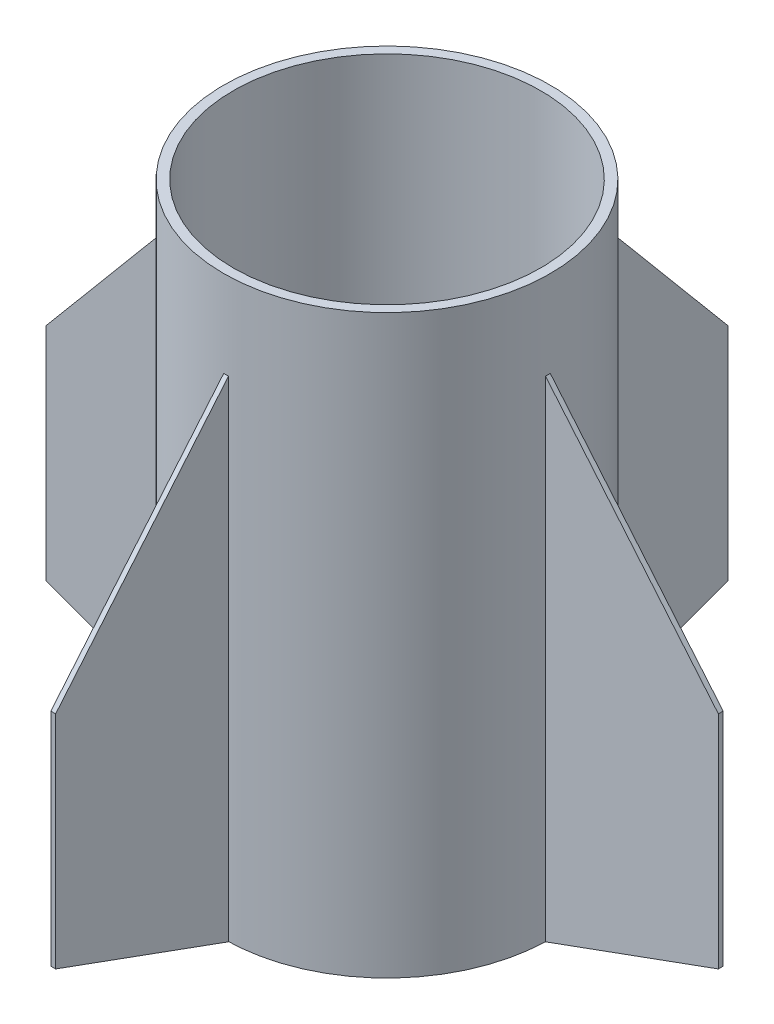
SolidWorks part; units mm, degrees
ref_plane "Front Plane" through (0, 0, 0) normal (0, 0, 1) x (1, 0, 0)
ref_plane "Top Plane" through (0, 0, 0) normal (0, 1, 0) x (1, 0, 0)
ref_plane "Right Plane" through (0, 0, 0) normal (1, 0, 0) x (0, 0, -1)
sketch "Sketch1" plane through (0, 0, 0) normal (0, 1, 0) x (1, 0, 0)
  circle A0 centre (0, 0) radius 101.6
  circle A1 centre (0, 0) radius 107.95
  dimension "D1" = 203.2
extrude "Boss-Extrude1" add sketch "Sketch1" along normal blind 381
sketch "Sketch2" plane through (0, 0, 0) normal (1, 0, 0) x (0, 0, -1)
  line L0 (-107.95, 323.85) -> (-222.25, 187.6577)
  line L1 (-107.95, 381) -> (-107.95, 0) construction
  line L2 (-222.25, 187.6577) -> (-222.25, 41.6077)
  line L3 (-222.25, 41.6077) -> (-107.95, 0)
  line L4 (-107.95, 0) -> (-107.95, 323.85)
  line L5 (0, 0) -> (0, 544.109) construction
  dimension "D1" = 114.3
  dimension "D2" = 177.8
  dimension "D3" = 323.85
  dimension "D4" = 146.05
extrude "Boss-Extrude2" add sketch "Sketch2" along normal blind 3.175 separate body
sketch "Sketch5" plane through (0, 0, 0) normal (1, 0, 0) x (0, 0, -1)
  line L0 (107.95, 323.85) -> (222.25, 187.6577)
  line L1 (107.95, 0) -> (107.95, 381) construction
  line L2 (222.25, 187.6577) -> (222.25, 41.6077)
  line L3 (222.25, 41.6077) -> (107.95, 0)
  line L4 (107.95, 0) -> (107.95, 381) construction
  line L5 (107.95, 323.85) -> (107.95, 0)
  dimension "D1" = 323.85
  dimension "D2" = 177.8
  dimension "D3" = 114.3
  dimension "D4" = 146.05
extrude "Boss-Extrude3" add sketch "Sketch5" along normal blind 3.175 separate body
sketch "Sketch6" plane through (0, 0, 0) normal (0, 0, 1) x (1, 0, 0)
  line L0 (-107.95, 323.85) -> (-222.25, 187.6577)
  line L1 (-107.95, 381) -> (-107.95, 0) construction
  line L2 (-222.25, 187.6577) -> (-222.25, 41.6077)
  line L3 (-222.25, 41.6077) -> (-107.95, 0)
  line L4 (-107.95, 323.85) -> (-107.95, 0)
  dimension "D1" = 146.05
  dimension "D2" = 177.8
  dimension "D3" = 323.85
  dimension "D4" = 114.3
extrude "Boss-Extrude4" add sketch "Sketch6" along normal blind 3.175 separate body
sketch "Sketch7" plane through (0, 0, 0) normal (0, 0, 1) x (1, 0, 0)
  line L0 (107.95, 323.85) -> (222.25, 187.6577)
  line L1 (107.95, 0) -> (107.95, 381) construction
  line L2 (222.25, 187.6577) -> (222.25, 41.6077)
  line L3 (222.25, 41.6077) -> (107.95, 0)
  line L4 (107.95, 0) -> (107.95, 323.85)
  dimension "D1" = 114.3
  dimension "D2" = 146.05
  dimension "D3" = 177.8
  dimension "D4" = 323.85
extrude "Boss-Extrude5" add sketch "Sketch7" along normal blind 3.175 separate body
